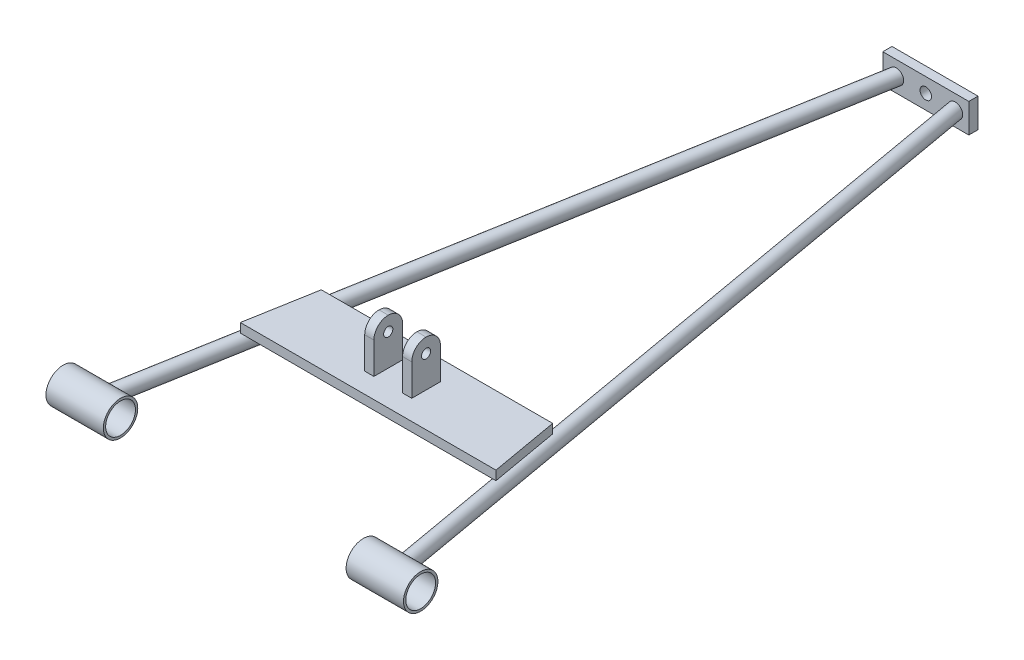
SolidWorks part; units mm, degrees
ref_plane "Front Plane" through (0, 0, 0) normal (0, 0, 1) x (1, 0, 0)
ref_plane "Top Plane" through (0, 0, 0) normal (0, 1, 0) x (1, 0, 0)
ref_plane "Right Plane" through (0, 0, 0) normal (1, 0, 0) x (0, 0, -1)
sketch "Sketch1" plane through (0, 0, 0) normal (0, 1, 0) x (1, 0, 0)
  line L0 (0, -35.7461) -> (0, 70.0445) construction
  line L1 (-130.7962, 0) -> (-25, 600)
  line L2 (130.7962, 0) -> (25, 600)
  line L3 (-12.8708, 600) -> (14.0839, 600) construction
  line L4 (-33.9598, 0) -> (50.1307, 0) construction
  line L5 (-155.7962, 0) -> (-105.7962, 0)
  line L6 (105.7962, 0) -> (155.7962, 0)
  point P11 (-130.7962, 0)
  point P16 (130.7962, 0)
  dimension "D1" = 600
  dimension "D2" = 10
  dimension "D3" = 50
  dimension "D4" = 50
sweep "Sweep2" add path "Sketch1" circular profile diameter 12.7 parameters "D3"=12.7
sketch "Sketch78" plane through (0, 0, 0) normal (0, 1, 0) x (1, 0, 0)
  line L0 (105.7962, 0) -> (155.7962, 0) construction
  line L1 (-155.7962, 0) -> (-105.7962, 0) construction
  line L2 (130.7962, 0) -> (25, 600) construction
  line L3 (-130.7962, 0) -> (-25, 600) construction
  line L4 (105.7962, 0) -> (155.7962, 0)
  line L5 (-155.7962, 0) -> (-105.7962, 0)
  line L6 (130.7962, 0) -> (25, 600)
  line L7 (-130.7962, 0) -> (-25, 600)
sweep "Sweep3" add path "Sketch78" circular profile diameter 12.7 parameters "D3"=12.7
sketch "Sketch87" plane through (0, 0, 0) normal (0, 1, 0) x (1, 0, 0)
  line L0 (105.7962, 0) -> (155.7962, 0) construction
  line L1 (-155.7962, 0) -> (-105.7962, 0) construction
  line L2 (130.7962, 0) -> (25, 600) construction
  line L3 (-130.7962, 0) -> (-25, 600) construction
  line L4 (105.7962, 0) -> (155.7962, 0)
  line L5 (-155.7962, 0) -> (-105.7962, 0)
  line L6 (130.7962, 0) -> (25, 600)
  line L7 (-130.7962, 0) -> (-25, 600)
sweep "Sweep-Thin2" add path "Sketch87" circular profile diameter 30 parameters "D1"=2, "D3"=30
sketch "Sketch140" plane through (0, 0, 0) normal (0, 1, 0) x (1, 0, 0)
  line L0 (-130.7962, 0) -> (-25, 600) construction
  line L1 (130.7962, 0) -> (25, 600) construction
  line L2 (-155.7962, 0) -> (-105.7962, 0) construction
  line L3 (105.7962, 0) -> (155.7962, 0) construction
  line L4 (-130.7962, 0) -> (-25, 600)
  line L5 (130.7962, 0) -> (25, 600)
  line L6 (-155.7962, 0) -> (-105.7962, 0)
  line L7 (105.7962, 0) -> (155.7962, 0)
sweep "Sweep-Thin3" add path "Sketch140" circular profile diameter 30 parameters "D1"=2, "D3"=30
sketch "Sketch161" plane through (0, 0, 0) normal (0, 1, 0) x (1, 0, 0)
  line L0 (105.7962, 0) -> (155.7962, 0) construction
  line L1 (-155.7962, 0) -> (-105.7962, 0) construction
  line L2 (130.7962, 0) -> (25, 600) construction
  line L3 (-130.7962, 0) -> (-25, 600) construction
  line L4 (105.7962, 0) -> (155.7962, 0)
  line L5 (-155.7962, 0) -> (-105.7962, 0)
  line L6 (130.7962, 0) -> (25, 600)
  line L7 (-130.7962, 0) -> (-25, 600)
  line L8 (-25, 600) -> (-25, 595) construction
  line L9 (0, 604) -> (0, 596) construction
  line L10 (-37.5, 604) -> (37.5, 604)
  line L11 (-37.5, 604) -> (-37.5, 596)
  line L12 (-37.5, 596) -> (37.5, 596)
  line L13 (37.5, 604) -> (37.5, 596)
  line L14 (-37.5, 600) -> (37.5, 600) construction
  dimension "D1" = 5
  dimension "D2" = 75
  dimension "D3" = 8
extrude "Boss-Extrude1" add sketch "Sketch161" along normal mid plane 25.4 separate body contours L13 L10 L11 L12 region at (0, 0, -600)
sketch "Sketch164" plane through (-37.5, 0, 0) normal (-1, 0, 0) x (0, 0, 1)
  line L4 (-604, -12.7) -> (-596, -12.7)
  line L5 (-596, -12.7) -> (-596, 12.7)
  line L6 (-596, 12.7) -> (-604, 12.7)
  line L7 (-604, 12.7) -> (-604, -12.7)
  line L8 (-604, -12.7) -> (-596, -12.7)
  line L9 (-596, -12.7) -> (-596, 12.7)
  line L10 (-596, 12.7) -> (-604, 12.7)
  line L11 (-604, 12.7) -> (-604, -12.7)
  dimension "D1" = 0
extrude "Cut-Extrude1" cut sketch "Sketch164" against normal through all
sketch "Sketch165" plane through (-155.7962, 0, 0) normal (-1, 0, 0) x (0, 0, 1)
  circle A0 centre (0, 0) radius 15 construction
  circle A1 centre (0, 0) radius 15
extrude "Cut-Extrude2" cut sketch "Sketch165" against normal through all
sketch "Sketch166" plane through (0, 0, -604) normal (0, 0, -1) x (-1, 0, 0)
  circle A0 centre (0, 0) radius 5
  dimension "D1" = 10
extrude "Cut-Extrude3" cut sketch "Sketch166" against normal blind 25.4
ref_plane "Plane1" through (0, 6.35, 0) normal (0, 1, 0) x (1, 0, 0)
sketch "Sketch167" plane through (0, 6.35, 0) normal (0, 1, 0) x (1, 0, 0)
  line L0 (105.7962, 0) -> (155.7962, 0) construction
  line L1 (-155.7962, 0) -> (-105.7962, 0) construction
  line L2 (130.7962, 0) -> (25, 600) construction
  line L3 (-130.7962, 0) -> (-25, 600) construction
  line L4 (105.7962, 0) -> (155.7962, 0)
  line L5 (-155.7962, 0) -> (-105.7962, 0)
  line L6 (130.7962, 0) -> (25, 600)
  line L7 (-130.7962, 0) -> (-25, 600)
  line L8 (100.8206, 170) -> (-100.8206, 170)
  line L9 (111.4002, 110) -> (-111.4002, 110)
  line L10 (100.8206, 170) -> (111.4002, 110)
  line L11 (-100.8206, 170) -> (-111.4002, 110)
  dimension "D1" = 60
  dimension "D2" = 110
extrude "Boss-Extrude2" add sketch "Sketch167" along normal blind 8 separate body contours L9 L6 L8 L7 region at (0, 6.35, -139.5015)
sketch "Sketch168" plane through (0, 14.35, 0) normal (0, 1, 0) x (1, 0, 0)
  line L0 (-130.7962, 0) -> (-25, 600) construction
  line L1 (130.7962, 0) -> (25, 600) construction
  line L2 (-155.7962, 0) -> (-105.7962, 0) construction
  line L3 (105.7962, 0) -> (155.7962, 0) construction
  line L4 (100.8206, 170) -> (-100.8206, 170)
  line L5 (-100.8206, 170) -> (-111.4002, 110)
  line L6 (-111.4002, 110) -> (111.4002, 110)
  line L7 (111.4002, 110) -> (100.8206, 170)
  line L8 (100.8206, 170) -> (-100.8206, 170)
  line L9 (-100.8206, 170) -> (-111.4002, 110)
  line L10 (-111.4002, 110) -> (111.4002, 110)
  line L11 (111.4002, 110) -> (100.8206, 170)
  line L12 (-130.7962, 0) -> (-25, 600)
  line L13 (130.7962, 0) -> (25, 600)
  line L14 (-155.7962, 0) -> (-105.7962, 0)
  line L15 (105.7962, 0) -> (155.7962, 0)
  line L16 (0, 170) -> (0, 110) construction
  line L17 (-20.5, 152.5) -> (20.5, 152.5)
  line L18 (-20.5, 152.5) -> (-20.5, 127.5)
  line L19 (-20.5, 127.5) -> (20.5, 127.5)
  line L20 (20.5, 152.5) -> (20.5, 127.5)
  line L21 (-20.5, 152.5) -> (20.5, 127.5) construction
  line L22 (-20.5, 127.5) -> (20.5, 152.5) construction
  line L23 (-20.5, 152.5) -> (-12.5, 152.5)
  line L24 (-20.5, 152.5) -> (-20.5, 127.5)
  line L25 (-20.5, 127.5) -> (-12.5, 127.5)
  line L26 (-12.5, 152.5) -> (-12.5, 127.5)
  line L27 (20.5, 127.5) -> (12.5, 127.5)
  line L28 (12.5, 152.5) -> (12.5, 127.5)
  line L29 (20.5, 152.5) -> (12.5, 152.5)
  line L30 (20.5, 152.5) -> (20.5, 127.5)
  point P12 (0, 140)
  point P18 (0, 170)
  point P20 (-106.1104, 140)
  dimension "D2" = 41
  dimension "D3" = 25
  dimension "D4" = 8
  dimension "D1" = 0
extrude "Boss-Extrude3" add sketch "Sketch168" along normal blind 40 contours L26 L17 L18 L19 | L17 L28 L19 L20 region at (-16.5, 14.35, -140) region at (16.5, 14.35, -140)
fillet "Fillet1" radius 12.5 4 edges at (16.5, 54.35, -152.5) (16.5, 54.35, -127.5) (-16.5, 54.35, -152.5) (-16.5, 54.35, -127.5)
sketch "Sketch170" plane through (20.5, 0, 0) normal (1, 0, 0) x (0, 0, -1)
  circle A0 centre (140, 41.85) radius 4
  dimension "D1" = 8
extrude "Cut-Extrude4" cut sketch "Sketch170" against normal through all
